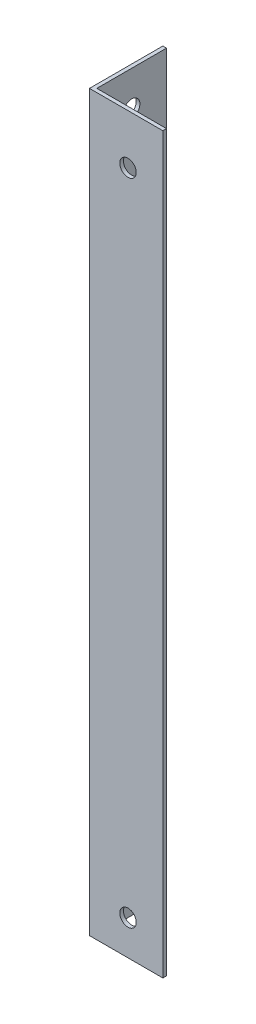
SolidWorks part; units mm, degrees
material "1060 Сплав"
ref_plane "Спереди" through (0, 0, 0) normal (0, 0, 1) x (1, 0, 0)
ref_plane "Сверху" through (0, 0, 0) normal (0, 1, 0) x (1, 0, 0)
ref_plane "Справа" through (0, 0, 0) normal (1, 0, 0) x (0, 0, -1)
sketch "Эскиз1" plane through (0, 0, 0) normal (0, 1, 0) x (1, 0, 0)
  line L0 (0, 0) -> (0, 20)
  line L1 (0, 20) -> (1, 20)
  line L2 (1, 20) -> (1, 1)
  line L3 (1, 1) -> (20, 1)
  line L4 (20, 1) -> (20, 0)
  line L5 (20, 0) -> (0, 0)
  dimension "D1" = 1
  dimension "D2" = 20
extrude "Бобышка-Вытянуть1" add sketch "Эскиз1" along normal blind 200
sketch "Эскиз2" plane through (0, 0, -1) normal (0, 0, -1) x (-1, 0, 0)
  circle A0 centre (-10.5, 9.5) radius 2.25 construction
  circle A1 centre (-10.5, 9.5) radius 2.25
extrude "Вырез-Вытянуть1" cut sketch "Эскиз2" against normal through all
sketch "Эскиз3" plane through (0, 0, -1) normal (0, 0, -1) x (-1, 0, 0)
  line L0 (0, 200) -> (0, 0) construction
  line L1 (0, 200) -> (-20, 200) construction
  circle A1 centre (-10.5, 186.5) radius 2.25
  dimension "D1" = 10.5
  dimension "D2" = 13.5
  dimension "D3" = 4.5
extrude "Вырез-Вытянуть2" cut sketch "Эскиз3" against normal through all
sketch "Эскиз4" plane through (1, 0, 0) normal (1, 0, 0) x (0, 0, -1)
  line L0 (10.5, 200) -> (10.5, 190.5) construction
  line L1 (1, 200) -> (20, 200) construction
  circle A0 centre (10.5, 190.5) radius 2.25
  dimension "D2" = 4.5
  dimension "D1" = 9.5
extrude "Вырез-Вытянуть3" cut sketch "Эскиз4" against normal through all
sketch "Эскиз5" plane through (1, 0, 0) normal (1, 0, 0) x (0, 0, -1)
  line L0 (10.5, 0) -> (10.5, 9.5) construction
  line L1 (1, 0) -> (20, 0) construction
  circle A0 centre (10.5, 9.5) radius 2.25
  dimension "D1" = 4.5
  dimension "D2" = 9.5
extrude "Вырез-Вытянуть4" cut sketch "Эскиз5" against normal through all
